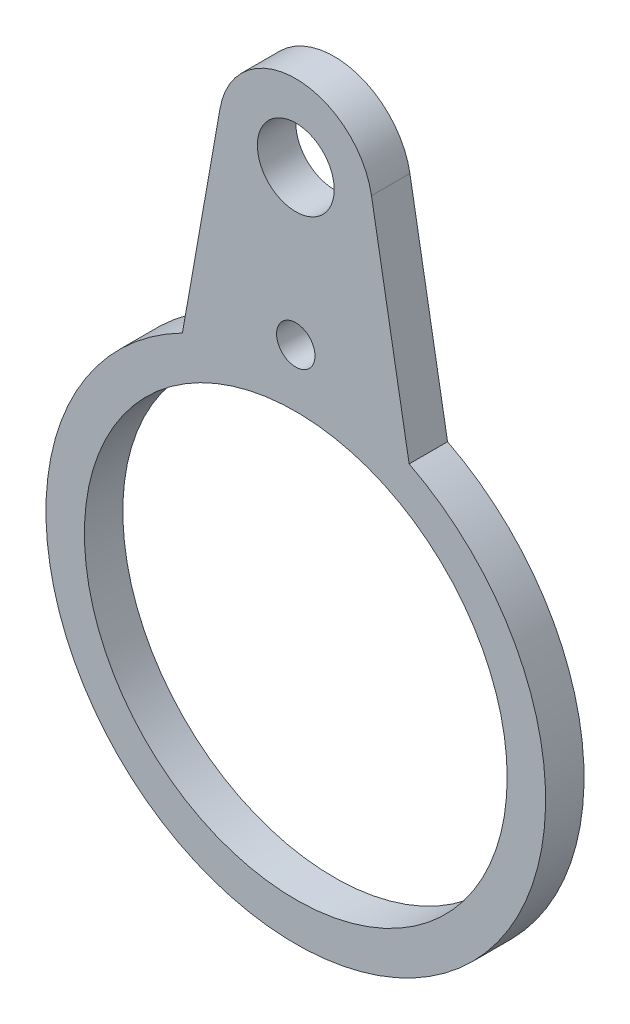
SolidWorks part; units mm, degrees
ref_plane "Front Plane" through (0, 0, 0) normal (0, 0, 1) x (1, 0, 0)
ref_plane "Top Plane" through (0, 0, 0) normal (0, 1, 0) x (1, 0, 0)
ref_plane "Right Plane" through (0, 0, 0) normal (1, 0, 0) x (0, 0, -1)
sketch "Sketch2" plane through (0, 0, 0) normal (0, 0, 1) x (1, 0, 0)
  line L0 (-19.7949, 2.8571) -> (-9.8974, 71.4286)
  line L1 (9.8974, 71.4286) -> (19.7949, 2.8571)
  line L2 (-2.5, 9.6825) -> (-2.5, 12)
  line L3 (-2.5, 12) -> (2.5, 12)
  line L4 (2.5, 12) -> (2.5, 9.6825)
  arc A0 (-19.7949, 2.8571) -> (19.7949, 2.8571) centre (0, 0) ccw
  arc A1 (-2.5, 9.6825) -> (2.5, 9.6825) centre (0, 0) ccw
  arc A2 (9.8974, 71.4286) -> (-9.8974, 71.4286) centre (0, 70) ccw
  circle A3 centre (0, 70) radius 5
  point P12 (0, 12)
  dimension "D1" = 20
  dimension "D2" = 40
  dimension "D3" = 10
  dimension "D4" = 20
  dimension "D5" = 70
  dimension "D6" = 12
  dimension "D7" = 5
extrude "Boss-Extrude1" add sketch "Sketch2" along normal blind 10
sketch "Sketch3" plane through (0, 0, 10) normal (0, 0, 1) x (1, 0, 0)
  circle A0 centre (0, 70) radius 10
  arc A1 (9.8974, 71.4286) -> (-9.8974, 71.4286) centre (0, 70) ccw construction
  circle A2 centre (0, 70) radius 5
  circle A3 centre (0, 70) radius 5 construction
extrude "Boss-Extrude2" add sketch "Sketch3" along normal blind 76.2
extrude "Boss-Extrude3" add sketch "Sketch2<2>" along normal blind 10 from surface starting at face at (10, 70, 86.2)
sketch "Sketch2<2>" plane through (0, 0, 0) normal (0, 0, 1) x (1, 0, 0) same geometry as "Sketch2"
sketch "Sketch5" plane through (0, 0, 96.2) normal (0, 0, 1) x (1, 0, 0)
  circle A0 centre (0, 0) radius 65
  dimension "D1" = 130
extrude "Boss-Extrude4" add sketch "Sketch5" against normal up to surface (10 mm away) up to face at (0, 5.9206, 86.2)
sketch "Sketch6" plane through (0, 0, 96.2) normal (0, 0, 1) x (1, 0, 0)
  circle A0 centre (0, 0) radius 55
  dimension "D1" = 110
extrude "Cut-Extrude1" cut sketch "Sketch6" against normal up to surface (10 mm away) contours A0 up to face at (0, 32.6245, 86.2)
sketch "Sketch7" plane through (0, 0, 86.2) normal (0, 0, -1) x (-1, 0, 0)
  circle A0 centre (0, 0) radius 80
  arc A1 (9.8974, 71.4286) -> (-9.8974, 71.4286) centre (0, 70) ccw construction
extrude "Cut-Extrude2" cut sketch "Sketch7" along normal through all
sketch "Sketch8" plane through (0, 0, 96.2) normal (0, 0, 1) x (1, 0, 0)
  line L0 (-29.4908, 57.9249) -> (-19.6962, 113.473)
  line L1 (29.4908, 57.9249) -> (19.6962, 113.473)
  line L2 (-29.4908, 57.9249) -> (29.4908, 57.9249) construction
  arc A0 (-10.9596, 64.0694) -> (10.9596, 64.0694) centre (0, 0) ccw construction
  arc A1 (-19.6962, 113.473) -> (19.6962, 113.473) centre (0, 110) cw
  arc A2 (-29.4908, 57.9249) -> (29.4908, 57.9249) centre (0, 0) cw
  arc A3 (9.8974, 71.4286) -> (-9.8974, 71.4286) centre (0, 70) ccw construction
  circle A4 centre (0, 110) radius 10
  circle A5 centre (0, 70) radius 5
  circle A6 centre (0, 70) radius 5 construction
  point P19 (0, 80)
  arc M9 (-10.9596, 64.0694) -> (10.9596, 64.0694) centre (0, 0) ccw
  line M10 (10.9596, 64.0694) -> (9.8974, 71.4286)
  arc M11 (9.8974, 71.4286) -> (-9.8974, 71.4286) centre (0, 70) ccw
  line M12 (-9.8974, 71.4286) -> (-10.9596, 64.0694)
  dimension "D1" = 20
  dimension "D3" = 20
  dimension "D2" = 30
  dimension "D4" = 80
extrude "Boss-Extrude6" add sketch "Sketch8" against normal up to surface (10 mm away) contours A1 L0 L1 A4 M9 M12 M11 M10 region at (0, 92.1421, 96.2) up to face at (55, 0, 86.2)
